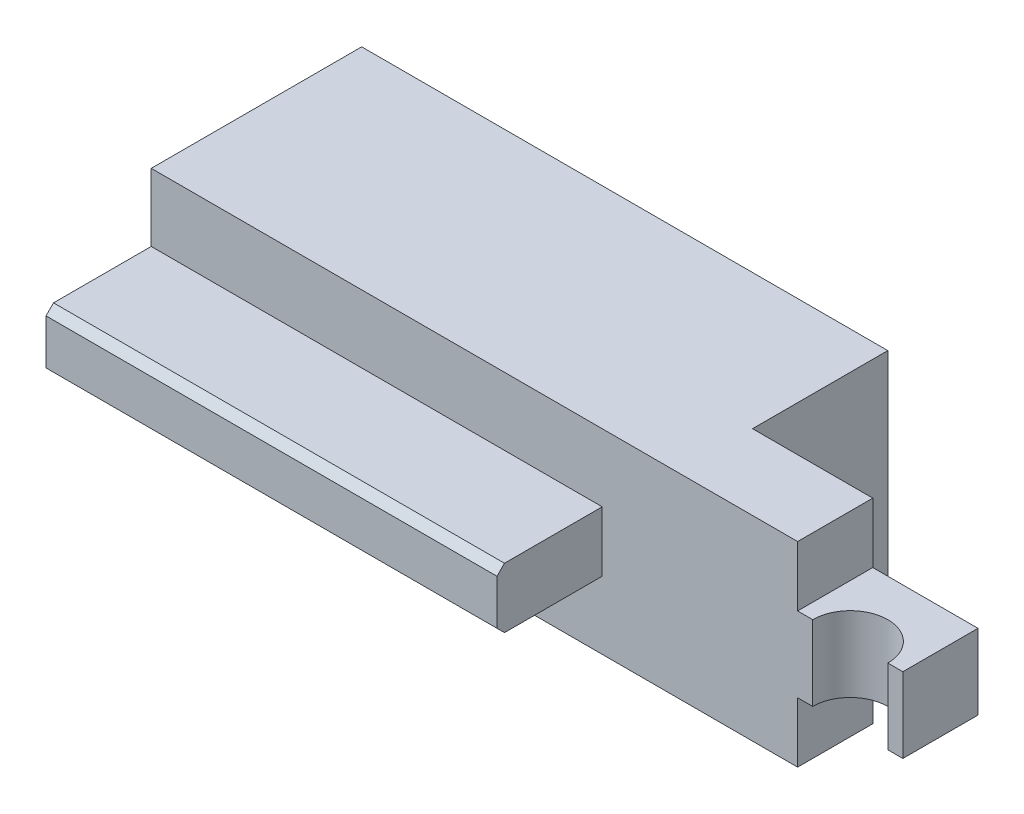
SolidWorks part; units mm, degrees
ref_plane "前视基准面" through (0, 0, 0) normal (0, 0, 1) x (1, 0, 0)
ref_plane "上视基准面" through (0, 0, 0) normal (0, 1, 0) x (1, 0, 0)
ref_plane "右视基准面" through (0, 0, 0) normal (1, 0, 0) x (0, 0, -1)
sketch "草图1" plane through (0, 0, 0) normal (1, 0, 0) x (0, 0, -1)
  line L0 (-15.5739, 0) -> (17.5206, 0) construction
  line L1 (0, 0) -> (0, 24.6123) construction
  line L2 (0, 0) -> (25, 0)
  line L3 (25, 0) -> (25, 17)
  line L4 (25, 17) -> (0, 17)
  line L5 (0, 17) -> (0, 0)
extrude "凸台-拉伸1" add sketch "草图1" along normal blind 50
sketch "草图2" plane through (0, 0, 0) normal (-1, 0, 0) x (0, 0, 1)
  line L0 (0, 17) -> (0, 11)
  line L1 (0, 17) -> (0, 0) construction
  line L2 (0, 11) -> (-11, 11)
  line L3 (-11, 11) -> (-11, 17)
  line L4 (-25, 17) -> (0, 17) construction
  line L5 (-11, 17) -> (0, 17)
  line L6 (-25, 8.5) -> (0, 8.5) construction
  line L7 (-25, 0) -> (-25, 17) construction
  line L8 (-11, 6) -> (-11, 0)
  line L9 (0, 6) -> (-11, 6)
  line L10 (0, 0) -> (0, 6)
  line L11 (-11, 0) -> (0, 0)
extrude "切除-拉伸1" cut sketch "草图2" against normal blind 50 contours L5 L0 L2 L3 | L8 L11 L10 L9
sketch "草图3" plane through (0, 11, 0) normal (0, 1, 0) x (1, 0, 0)
  line L0 (50, 0) -> (50, 11)
  line L1 (50, 11) -> (30, 11)
  line L2 (50, 11) -> (0, 11) construction
  line L3 (30, 11) -> (30, 0)
  line L4 (50, 0) -> (0, 0) construction
  line L5 (30, 0) -> (50, 0)
extrude "切除-拉伸2" cut sketch "草图3" against normal blind 50
sketch "草图4" plane through (0, 0, -25) normal (0, 0, -1) x (-1, 0, 0)
  line L0 (-50, 8.5) -> (0, 8.5) construction
  line L1 (-50, 0) -> (-50, 17) construction
  line L2 (0, 0) -> (0, 17) construction
  line L4 (-50, 11) -> (-43, 11)
  line L5 (-43, 11) -> (-43, 17)
  line L6 (-50, 17) -> (0, 17) construction
  line L7 (-43, 17) -> (-50, 17)
  line L8 (-50, 17) -> (-50, 11)
  line L9 (-50, 0) -> (-50, 6)
  line L10 (-43, 0) -> (-50, 0)
  line L11 (-43, 6) -> (-43, 0)
  line L12 (-50, 6) -> (-43, 6)
extrude "切除-拉伸3" cut sketch "草图4" against normal blind 50
sketch "草图5" plane through (0, 11, 0) normal (0, 1, 0) x (1, 0, 0)
  line L1 (50, 11) -> (50, 25) construction
  line L2 (50, 16) -> (43, 16)
  line L3 (43, 11) -> (43, 25) construction
  line L4 (43, 16) -> (43, 25)
  line L5 (43, 25) -> (50, 25)
  line L6 (50, 25) -> (50, 16)
extrude "切除-拉伸4" cut sketch "草图5" against normal blind 50 contours L2 L4 L5 L6
sketch "草图6" plane through (0, 11, 0) normal (0, 1, 0) x (1, 0, 0)
  line L0 (43, 11) -> (50, 11) construction
  circle A0 centre (46.5, 11) radius 2.5
extrude "切除-拉伸5" cut sketch "草图6" against normal blind 50
sketch "草图7" plane through (0, 0, 0) normal (-1, 0, 0) x (0, 0, 1)
  line L0 (0, 8.5) -> (-25, 8.5)
  line L1 (0, 11) -> (0, 6) construction
  line L2 (-25, 0) -> (-25, 17) construction
  line L3 (-25, 17) -> (-25, 15)
  line L4 (-25, 15) -> (-11, 15)
  line L5 (-11, 11) -> (-11, 17) construction
  line L6 (-11, 15) -> (-11, 17)
  line L7 (-11, 17) -> (-25, 17)
  line L8 (-11, 2) -> (-11, 0)
  line L9 (-25, 2) -> (-11, 2)
  line L10 (-25, 0) -> (-25, 2)
  line L11 (-11, 0) -> (-25, 0)
  line M6 (-11, 11) -> (-11, 17)
  line M7 (-11, 17) -> (-25, 17)
  line M8 (-25, 17) -> (-25, 0)
  line M9 (-25, 0) -> (-11, 0)
  line M10 (-11, 0) -> (-11, 6)
extrude "切除-拉伸8" cut sketch "草图7" against normal blind 50 contours L4 M8 M6 M7 | L9 M8 M9 M10 region at (0, 16, -18) region at (0, 1, -18)
sketch "草图10" plane through (0, 0, 0) normal (-1, 0, 0) x (0, 0, 1)
  line L0 (0, 11) -> (-4, 11)
  line L1 (0, 11) -> (-11, 11) construction
  line L2 (-4, 11) -> (-4, 6)
  line L3 (0, 6) -> (-11, 6) construction
  line L4 (-4, 6) -> (0, 6)
  line L5 (0, 6) -> (0, 11)
extrude "切除-拉伸9" cut sketch "草图10" against normal blind 50
sketch "草图11" plane through (0, 0, 0) normal (-1, 0, 0) x (0, 0, 1)
  line L0 (-22, 12) -> (-22, 5)
  line L3 (-22, 12) -> (-14, 12)
  line L4 (-14, 12) -> (-14, 5)
  line L5 (-14, 5) -> (-22, 5)
extrude "切除-拉伸10" cut sketch "草图11" against normal blind 30
sketch "草图12" plane through (0, 0, 0) normal (-1, 0, 0) x (0, 0, 1)
  line L0 (-4, 8.5) -> (-25, 8.5) construction
  line L1 (-4, 11) -> (-4, 6) construction
  line L2 (-25, 2) -> (-25, 15) construction
  line L3 (-4, 11) -> (-4, 10)
  line L4 (-4, 11) -> (-5, 11)
  line L5 (-4, 11) -> (-11, 11) construction
  line L6 (-5, 11) -> (-4, 10)
  line L7 (-4, 6) -> (-5, 6)
  line L8 (-4, 6) -> (-4, 7)
  line L9 (-5, 6) -> (-4, 7)
extrude "切除-拉伸11" cut sketch "草图12" against normal blind 50 contours L6 L3 L4 | L7 L9 L8
sketch "草图13" plane through (0, 0, 0) normal (-1, 0, 0) x (0, 0, 1)
  line L0 (-11, 11) -> (-11, 10.5)
  line L1 (-11, 10.5) -> (-4.5, 10.5)
  line L2 (-5, 11) -> (-4, 10) construction
  line L3 (-4.5, 10.5) -> (-5, 11)
  line L4 (-5, 11) -> (-11, 11)
  line L5 (-4, 8.5) -> (-25, 8.5) construction
  line L6 (-4, 10) -> (-4, 7) construction
  line L7 (-25, 2) -> (-25, 15) construction
  line L8 (-4.5, 6.5) -> (-5, 6)
  line L9 (-11, 6.5) -> (-4.5, 6.5)
  line L10 (-11, 6) -> (-11, 6.5)
  line L11 (-5, 6) -> (-11, 6)
extrude "切除-拉伸12" cut sketch "草图13" against normal blind 50
sketch "草图14" plane through (0, 0, -25) normal (0, 0, -1) x (-1, 0, 0)
  circle A0 centre (-3, 8.5) radius 1.55
  circle A1 centre (-11, 8.5) radius 1.55
extrude "切除-拉伸13" cut sketch "草图14" against normal blind 5 contours A0 | A1 | A1 region at (3, 8.5, -25) region at (11, 8.5, -25)
sketch "Skizze1" plane through (43, 0, 0) normal (1, 0, 0) x (0, 0, -1)
  line L1 (25, 15) -> (11, 15) construction
  line L5 (25, 2) -> (11, 2) construction
  line L7 (16, 15) -> (16, 2)
  line L9 (16, 15) -> (25, 15)
  line L10 (25, 15) -> (25, 2)
  line L11 (25, 2) -> (16, 2)
extrude "Schnitt-Linear austragen1" cut sketch "Skizze1" against normal blind 8
sketch "Skizze2" plane through (0, 0, -25) normal (0, 0, -1) x (-1, 0, 0)
  line L0 (0, 8.5) -> (-3, 8.5)
  line L1 (0, 2) -> (0, 15) construction
  line L2 (-3, 10.05) -> (-3, 8.5)
  line L3 (-3, 8.5) -> (-11, 8.5)
  circle A1 centre (-3, 8.5) radius 1.55 construction
